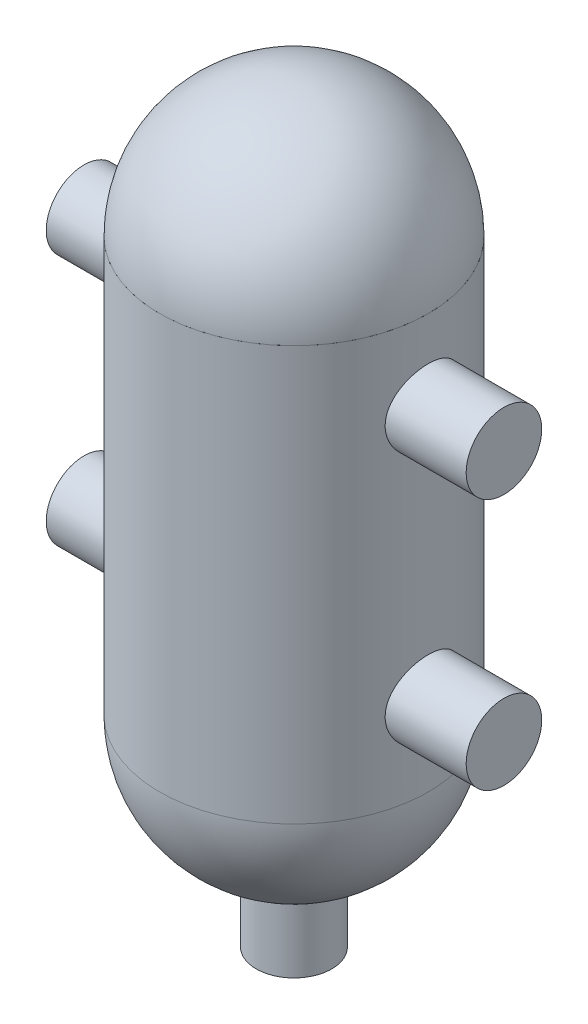
SolidWorks part; units mm, degrees
note: The reader was unsure of these and kept them because the rebuilt part matched: shared geometry of "Sketch1<3>".
ref_plane "Front" through (0, 0, 0) normal (0, 0, 1) x (1, 0, 0)
ref_plane "Top" through (0, 0, 0) normal (0, 1, 0) x (1, 0, 0)
ref_plane "Right" through (0, 0, 0) normal (1, 0, 0) x (0, 0, -1)
sketch "Sketch1" plane through (0, 0, 0) normal (0, 0, 1) x (1, 0, 0)
  line L1 (80, 123.33) -> (80, 0)
  line L4 (0, 0) -> (80, 0) construction
  line L5 (70, 113.33) -> (70, 0)
  line L6 (0, 203.33) -> (0, 193.33)
  line L7 (80, 0) -> (70, 0)
  line L8 (0, -203.33) -> (0, -193.33)
  line L9 (70, -123.33) -> (70, 0)
  line L10 (80, -123.33) -> (80, 0)
  line L11 (70, 123.33) -> (80, 123.33)
  line L12 (70, 123.33) -> (70, 0) construction
  line L13 (0, 123.33) -> (80, 123.33)
  line L14 (0, 123.33) -> (0, 113.33)
  line L15 (0, 113.33) -> (80, 113.33)
  line L16 (80, 123.33) -> (80, 113.33)
  arc A0 (0, 203.33) -> (80, 123.33) centre (0, 123.33) cw
  arc A4 (0, 193.33) -> (70, 123.33) centre (0, 123.33) cw
  arc A5 (0, -193.33) -> (70, -123.33) centre (0, -123.33) ccw
  arc A6 (0, -203.33) -> (80, -123.33) centre (0, -123.33) ccw
  dimension "D1" = 80
  dimension "D2" = 123.33
  dimension "D4" = 10
  dimension "D3" = 10
revolve "Revolve1" add sketch "Sketch1" angle 360 about L6
revolve "Revolve2" add sketch "Sketch1<3>" angle 360 about L6
sketch "Sketch1<3>" plane through (0, 0, 0) normal (0, 0, 1) x (1, 0, 0) same geometry as "Sketch1"
sketch "Sketch2" plane through (0, 0, 0) normal (1, 0, 0) x (0, 0, -1)
  circle A0 centre (0, 75) radius 22.5
  circle A1 centre (0, -75) radius 22.5
  dimension "D1" = 45
  dimension "D3" = 45
  dimension "D2" = 75
  dimension "D4" = 75
extrude "Boss-Extrude1" add sketch "Sketch2" along normal mid plane 250
ref_plane "Plane1" through (0, -123.33, 0) normal (0, 1, 0) x (1, 0, 0)
sketch "Sketch3" plane through (0, -123.33, 0) normal (0, 1, 0) x (1, 0, 0)
  circle A0 centre (0, 0) radius 22.5
  dimension "D1" = 45
extrude "Boss-Extrude2" add sketch "Sketch3" against normal blind 120
